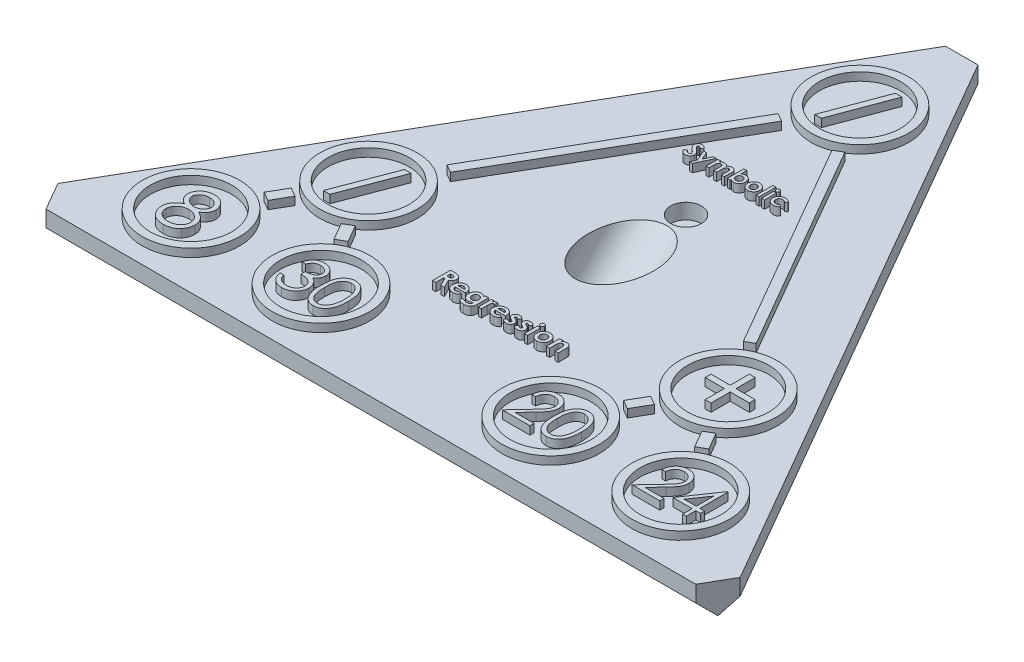
SolidWorks part; units mm, degrees
ref_plane "Front Plane" through (0, 0, 0) normal (0, 0, 1) x (1, 0, 0)
ref_plane "Top Plane" through (0, 0, 0) normal (0, 1, 0) x (1, 0, 0)
ref_plane "Right Plane" through (0, 0, 0) normal (1, 0, 0) x (0, 0, -1)
sketch "Sketch2" plane through (0, 0, 0) normal (0, 1, 0) x (1, 0, 0)
  line L0 (3.175, 75.1566) -> (-3.175, 75.1566)
  line L1 (-3.175, 75.1566) -> (-66.675, -34.8287)
  line L2 (-63.5, -40.3279) -> (63.5, -40.3279)
  line L3 (66.675, -34.8287) -> (3.175, 75.1566)
  line L4 (63.5, -40.3279) -> (66.675, -34.8287)
  line L5 (-66.675, -34.8287) -> (-63.5, -40.3279)
  circle A0 centre (0, 0) radius 40.3279 construction
  point P2 (0, 80.6558)
  point P3 (-69.85, -40.3279)
  point P4 (69.85, -40.3279)
  dimension "D1" = 139.7
extrude "Boss-Extrude1" add sketch "Sketch2" against normal blind 3.175
sketch "Sketch3" plane through (0, 0, 0) normal (0, 1, 0) x (1, 0, 0)
  line L0 (0, 55.2558) -> (0, 29.8558) construction
  line L1 (-15.4161, 29.8558) -> (15.4161, 29.8558) construction
  line L2 (0, 29.8558) -> (0, -16.2198) construction
  line L3 (-18.6015, -16.2198) -> (18.6015, -16.2198) construction
  line L5 (-47.853, -27.6279) -> (-35.153, -5.6309) construction
  line L6 (-35.153, -5.6309) -> (-22.453, -27.6279) construction
  line L7 (-22.453, -27.6279) -> (-47.853, -27.6279) construction
  line L8 (35.153, -5.6309) -> (22.453, -27.6279) construction
  line L9 (22.453, -27.6279) -> (47.853, -27.6279) construction
  line L10 (47.853, -27.6279) -> (35.153, -5.6309) construction
  line L11 (-63.5, -40.3279) -> (63.5, -40.3279) construction
  line L13 (-3.175, 75.1566) -> (-66.675, -34.8287) construction
  line L14 (66.675, -34.8287) -> (3.175, 75.1566) construction
  line L15 (0, 55.2558) -> (0, 50.9403) construction
  line L16 (-35.153, -5.6309) -> (-35.153, -9.9464) construction
  line L17 (-47.853, -27.6279) -> (-47.853, -32.7771) construction
  line L18 (-22.453, -27.6279) -> (-22.453, -31.9435) construction
  line L19 (35.153, -5.6309) -> (35.153, -11.6942) construction
  line L20 (22.453, -27.6279) -> (22.453, -31.3004) construction
  line L21 (47.853, -27.6279) -> (47.853, -31.3004) construction
  line L22 (-6.6618, 50.9403) -> (6.6618, 50.9403) construction
  line L23 (-41.8148, -9.9464) -> (-28.4911, -9.9464) construction
  line L24 (-53.8936, -32.7771) -> (-41.8123, -32.7771) construction
  line L25 (-29.1148, -31.9435) -> (-15.7911, -31.9435) construction
  line L26 (30.0305, -11.6942) -> (40.2754, -11.6942) construction
  line L27 (15.4161, -31.3004) -> (29.4898, -31.3004) construction
  line L28 (40.8161, -31.3004) -> (54.8898, -31.3004) construction
  circle A0 centre (0, 55.2558) radius 9.525 construction
  circle A1 centre (-47.853, -27.6279) radius 9.525 construction
  circle A2 centre (-22.453, -27.6279) radius 9.525 construction
  circle A3 centre (22.453, -27.6279) radius 9.525 construction
  circle A4 centre (47.853, -27.6279) radius 9.525 construction
  circle A5 centre (-35.153, -5.6309) radius 9.525 construction
  circle A6 centre (35.153, -5.6309) radius 9.525 construction
  circle A7 centre (0, 55.2558) radius 7.9375 construction
  circle A8 centre (-35.153, -5.6309) radius 7.9375 construction
  circle A9 centre (35.153, -5.6309) radius 7.9375 construction
  circle A10 centre (-47.853, -27.6279) radius 7.9375 construction
  circle A11 centre (-22.453, -27.6279) radius 7.9375 construction
  circle A12 centre (22.453, -27.6279) radius 7.9375 construction
  circle A13 centre (47.853, -27.6279) radius 7.9375 construction
  text T0 "/" font "Century Gothic" height 9.525
  text T1 "/" font "Century Gothic" height 9.525
  text T2 "8" font "Century Gothic" height 9.525
  text T3 "30" font "Century Gothic" height 7.9375
  text T4 "+" font "Century Gothic" height 12.7
  text T5 "20\r\n" font "Century Gothic" height 7.9375
  text T6 "24\r\n" font "Century Gothic" height 7.9375
  text T7 "Symbolic" font "Century Gothic" height 3.175
  text T8 "<b>Regression</b>"
  point P36 (0, 50.9403)
  point P41 (-35.153, -9.9464)
  point P43 (-47.853, -32.7771)
  point P46 (-22.453, -31.9435)
  point P51 (35.153, -11.6942)
  point P54 (22.453, -31.3004)
  point P57 (47.853, -31.3004)
  point P62 (0, 29.8558)
  point P63 (0, 29.8558)
  point P64 (0, 29.8558)
  point P70 (0, -16.2198)
  dimension "D1" = 19.05
  dimension "D2" = 1.5875
  dimension "D3" = 25.4
  dimension "D4" = 12.7
  dimension "D5" = 12.7
  dimension "D6" = 12.7
  dimension "D7" = 12.7
  dimension "D8" = 12.7
  dimension "D9" = 12.7
  dimension "D10" = 25.4
sketch "Sketch4" plane through (0, -3.175, 0) normal (0, -1, 0) x (1, 0, 0)
  line L6 (-66.675, 34.8287) -> (-3.175, -75.1566)
  line L7 (-3.175, -75.1566) -> (3.175, -75.1566)
  line L8 (3.175, -75.1566) -> (66.675, 34.8287)
  line L9 (66.675, 34.8287) -> (63.5, 40.3279)
  line L10 (63.5, 40.3279) -> (-63.5, 40.3279)
  line L11 (-63.5, 40.3279) -> (-66.675, 34.8287)
  line L12 (-66.675, 34.8287) -> (-3.175, -75.1566)
  line L13 (-3.175, -75.1566) -> (3.175, -75.1566)
  line L14 (3.175, -75.1566) -> (66.675, 34.8287)
  line L15 (66.675, 34.8287) -> (63.5, 40.3279)
  line L16 (63.5, 40.3279) -> (-63.5, 40.3279)
  line L17 (-63.5, 40.3279) -> (-66.675, 34.8287)
  dimension "D1" = 0
extrude "Boss-Extrude3" add sketch "Sketch4" along normal blind 12.7
chamfer "Chamfer1" distance 12.7 angle 45 3 edges at (0, -15.875, 40.3279) (34.925, -15.875, -20.164) (-34.925, -15.875, -20.164)
extrude "Boss-Extrude4" add sketch "Sketch3" along normal blind 1.5875
sketch "Sketch9" plane through (0, 0, 0) normal (0, 1, 0) x (1, 0, 0)
  line L0 (-35.153, -5.6309) -> (0, 55.2558) construction
  line L1 (0, 55.2558) -> (35.153, -5.6309) construction
  line L5 (-47.853, -27.6279) -> (-35.153, -5.6309) construction
  line L6 (-35.153, -5.6309) -> (-22.453, -27.6279) construction
  line L7 (-22.453, -27.6279) -> (-47.853, -27.6279) construction
  line L8 (35.153, -5.6309) -> (22.453, -27.6279) construction
  line L9 (22.453, -27.6279) -> (47.853, -27.6279) construction
  line L10 (47.853, -27.6279) -> (35.153, -5.6309) construction
  line L12 (-4.9337, 44.8646) -> (-6.5323, 45.7875)
  line L13 (-4.9337, 44.8646) -> (-28.6207, 3.8375)
  line L15 (0, 55.2558) -> (0, 50.9403) construction
  line L16 (-35.153, -5.6309) -> (-35.153, -9.9464) construction
  line L17 (-47.853, -27.6279) -> (-47.853, -32.7771) construction
  line L18 (-22.453, -27.6279) -> (-22.453, -31.9435) construction
  line L19 (35.153, -5.6309) -> (35.153, -11.6942) construction
  line L20 (22.453, -27.6279) -> (22.453, -31.3004) construction
  line L21 (47.853, -27.6279) -> (47.853, -31.3004) construction
  line L22 (-6.6618, 50.9403) -> (6.6618, 50.9403) construction
  line L23 (-41.8148, -9.9464) -> (-28.4911, -9.9464) construction
  line L24 (-53.8936, -32.7771) -> (-41.8123, -32.7771) construction
  line L25 (-29.1148, -31.9435) -> (-15.7911, -31.9435) construction
  line L26 (30.0305, -11.6942) -> (40.2754, -11.6942) construction
  line L27 (15.4161, -31.3004) -> (29.4898, -31.3004) construction
  line L28 (40.8161, -31.3004) -> (54.8898, -31.3004) construction
  line L32 (-6.5323, 45.7875) -> (-30.2193, 4.7604)
  line L33 (-28.6207, 3.8375) -> (-30.2193, 4.7604)
  line L34 (-43.4571, -17.7372) -> (-41.701, -18.751)
  line L35 (-43.4571, -17.7372) -> (-41.5207, -14.3832)
  line L36 (-41.701, -18.751) -> (-39.7646, -15.397)
  line L37 (-41.5207, -14.3832) -> (-39.7646, -15.397)
  line L38 (-43.4571, -17.7372) -> (-39.7646, -15.397) construction
  line L39 (-41.701, -18.751) -> (-41.5207, -14.3832) construction
  line L40 (-28.676, -18.877) -> (-26.92, -17.8631)
  line L41 (-28.676, -18.877) -> (-30.6125, -15.523)
  line L42 (-26.92, -17.8631) -> (-28.8564, -14.5091)
  line L43 (-30.6125, -15.523) -> (-28.8564, -14.5091)
  line L44 (-28.676, -18.877) -> (-28.8564, -14.5091) construction
  line L45 (-26.92, -17.8631) -> (-30.6125, -15.523) construction
  line L50 (-4.9337, 44.8646) -> (-30.2193, 4.7604) construction
  line L51 (-6.5323, 45.7875) -> (-28.6207, 3.8375) construction
  line L56 (0, -1.7463) -> (0, 1.7463) construction
  line L57 (28.676, -18.877) -> (26.92, -17.8631)
  line L58 (26.92, -17.8631) -> (28.8564, -14.5091)
  line L59 (30.6125, -15.523) -> (28.8564, -14.5091)
  line L60 (28.676, -18.877) -> (30.6125, -15.523)
  line L61 (43.4571, -17.7372) -> (41.701, -18.751)
  line L62 (43.4571, -17.7372) -> (41.5207, -14.3832)
  line L63 (41.5207, -14.3832) -> (39.7646, -15.397)
  line L64 (41.701, -18.751) -> (39.7646, -15.397)
  line L65 (28.6207, 3.8375) -> (30.2193, 4.7604)
  line L66 (6.5323, 45.7875) -> (30.2193, 4.7604)
  line L67 (4.9337, 44.8646) -> (6.5323, 45.7875)
  line L68 (4.9337, 44.8646) -> (28.6207, 3.8375)
  circle A0 centre (0, 55.2558) radius 9.525
  circle A1 centre (-47.853, -27.6279) radius 9.525
  circle A2 centre (-22.453, -27.6279) radius 9.525
  circle A3 centre (22.453, -27.6279) radius 9.525
  circle A4 centre (47.853, -27.6279) radius 9.525
  circle A5 centre (-35.153, -5.6309) radius 9.525
  circle A6 centre (35.153, -5.6309) radius 9.525
  circle A7 centre (0, 55.2558) radius 7.9375
  circle A8 centre (-35.153, -5.6309) radius 7.9375
  circle A9 centre (35.153, -5.6309) radius 7.9375
  circle A10 centre (-47.853, -27.6279) radius 7.9375
  circle A11 centre (-22.453, -27.6279) radius 7.9375
  circle A12 centre (22.453, -27.6279) radius 7.9375
  circle A13 centre (47.853, -27.6279) radius 7.9375
  point P22 (-17.5765, 24.8125)
  point P23 (-41.6108, -16.5671)
  point P36 (0, 50.9403)
  point P41 (-35.153, -9.9464)
  point P43 (-47.853, -32.7771)
  point P46 (-22.453, -31.9435)
  point P50 (-28.7662, -16.693)
  point P51 (35.153, -11.6942)
  point P54 (22.453, -31.3004)
  point P57 (47.853, -31.3004)
  dimension "D1" = 19.05
  dimension "D2" = 1.5875
  dimension "D3" = 25.4
extrude "Boss-Extrude5" add sketch "Sketch9" along normal blind 1.5875
sketch "Sketch10" plane through (0, -15.875, 0) normal (0, -1, 0) x (1, 0, 0)
  line L0 (0, 27.6279) -> (0, 7.3079) construction
  line L1 (47.853, 27.6279) -> (-47.853, 27.6279) construction
  point P5 (0, 0)
  dimension "D1" = 20.32
ref_plane "Plane1" through (0, -21.7515, 21.7515) normal (0, -0.7071, 0.7071) x (-1, 0, 0)
sketch "Sketch11" plane through (0, -21.7515, 21.7515) normal (0, -0.7071, 0.7071) x (-1, 0, 0)
  circle A0 centre (0, 6.0578) radius 3.9688
  circle A1 centre (0, 6.0578) radius 2.3813
  dimension "D1" = 7.9375
  dimension "D2" = 4.7625
extrude "Cut-Extrude1" cut sketch "Sketch11" against normal blind 19.05 contours A0 A1 | A1 region at (3.8565, -26.035, 17.4679)
extrude "Cut-Extrude2" cut sketch "Sketch11<3>" against normal through all contours A1 region at (0, -26.035, 17.4679)
sketch "Sketch11<3>" plane through (0, -21.7515, 21.7515) normal (0, -0.7071, 0.7071) x (-1, 0, 0) same geometry as "Sketch11"
ref_plane "Plane2" through (0, 14.1696, -14.1696) normal (0, -0.7071, 0.7071) x (-1, 0, 0)
sketch "Sketch12" plane through (0, 14.1696, -14.1696) normal (0, -0.7071, 0.7071) x (-1, 0, 0)
  circle A0 centre (0, 6.0578) radius 6.35
  circle A1 centre (0, 6.0578) radius 2.3813
  circle A2 centre (0, 6.0578) radius 2.3813 construction
  circle A3 centre (0, 6.0578) radius 3.9688
  circle A4 centre (0, 6.0578) radius 3.9688 construction
  dimension "D3" = 12.7
  dimension "D1" = 0
  dimension "D2" = 0
extrude "Cut-Extrude3" cut sketch "Sketch12" along normal blind 29.21
sketch "Sketch13" plane through (0, 0, 0) normal (0, 1, 0) x (1, 0, 0)
  circle A0 centre (0, 21.2671) radius 3 construction
  circle A1 centre (0, 21.2671) radius 3
extrude "Cut-Extrude4" cut sketch "Sketch13" against normal blind 3
